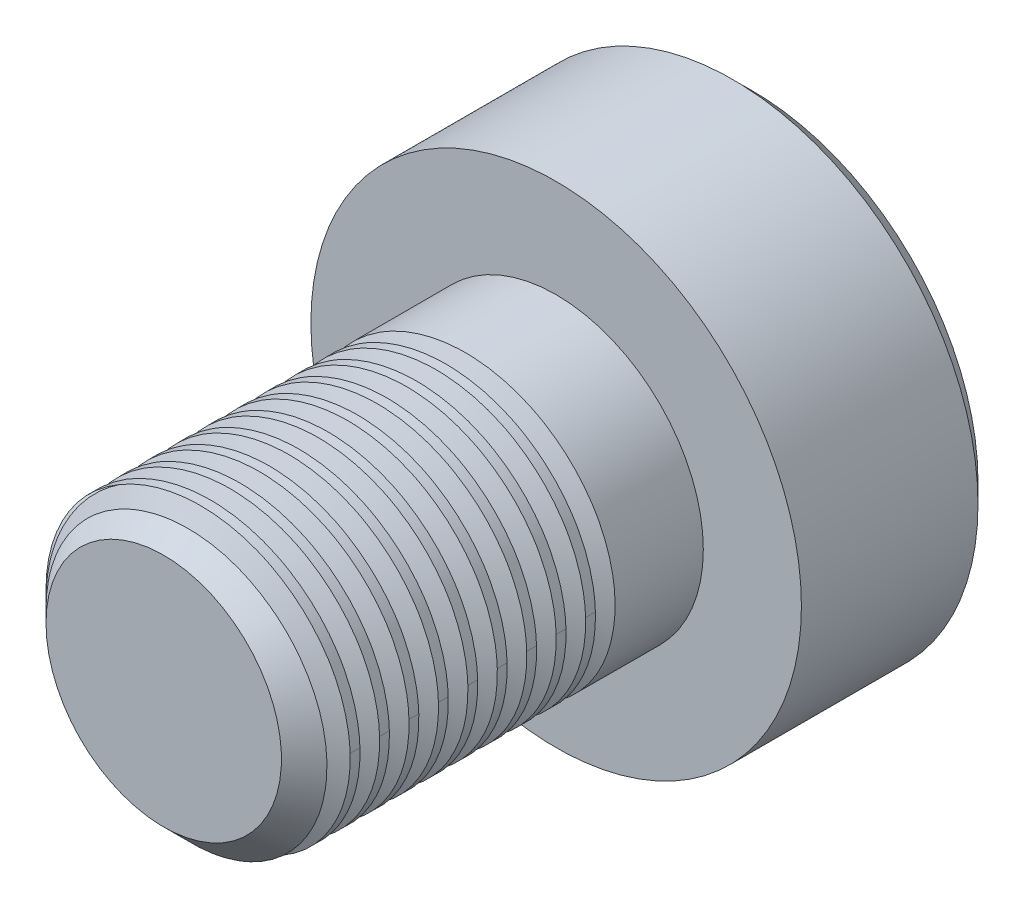
SolidWorks part; units mm, degrees
ref_plane "Front Plane" through (0, 0, 0) normal (0, 0, 1) x (1, 0, 0)
ref_plane "Top Plane" through (0, 0, 0) normal (0, 1, 0) x (1, 0, 0)
ref_plane "Right Plane" through (0, 0, 0) normal (1, 0, 0) x (0, 0, -1)
sketch "Sketch1" plane through (0, 0, 0) normal (0, 1, 0) x (1, 0, 0)
  line L0 (0, 0) -> (0, 34.3069) construction
  line L1 (0, 0) -> (-1.5, 0)
  line L2 (-1.5, 0) -> (-1.5, 4)
  line L3 (-1.5, 4) -> (-2.5, 4)
  line L4 (-2.5, 4) -> (-2.5, 6)
  line L5 (-2.5, 6) -> (0, 6)
  line L6 (0, 0) -> (0, 6)
revolve "Revolve1" add sketch "Sketch1" angle 360 about L0
sketch "Sketch2" plane through (0, 0, -6) normal (0, 0, -1) x (-1, 0, 0)
  line L1 (-2, 0) -> (-1, -1.7321)
  line L2 (-1, -1.7321) -> (1, -1.7321)
  line L3 (1, -1.7321) -> (2, 0)
  line L4 (2, 0) -> (1, 1.7321)
  line L5 (1, 1.7321) -> (-1, 1.7321)
  line L6 (-1, 1.7321) -> (-2, 0)
  circle A0 centre (0, 0) radius 1.7321 construction
extrude "Cut-Extrude1" cut sketch "Sketch2" against normal blind 1.5
fillet "Fillet1" radius 0.2 6 edges at (-1.5, 0.866, -6) (-1.5, -0.866, -6) (0, -1.7321, -6) (1.5, -0.866, -6) (1.5, 0.866, -6) (0, 1.7321, -6)
chamfer "Chamfer1" distance 0.1 angle 45 6 edges at (1.5, -0.866, -4.5) (0, -1.7321, -4.5) (-1.5, -0.866, -4.5) (-1.5, 0.866, -4.5) (0, 1.7321, -4.5) (1.5, 0.866, -4.5)
chamfer "Chamfer2" distance 0.2 angle 45 1 edges at (2.5, 0, -6)
chamfer "Chamfer3" distance 0.3 angle 45 1 edges at (1.5, 0, 0)
sketch "Sketch3" plane through (0, 0, 0) normal (0, 0, 1) x (1, 0, 0)
  circle A0 centre (0, 0) radius 1.3
curve "Helix/Spiral1" pitch 0.3 height 3.075 radius 1.3 centre (0, 0, 0) axis (0, 0, -1) start towards (1, 0, 0)
sketch "Sketch4" plane through (0, 0, 0) normal (0, 1, 0) x (1, 0, 0)
  line L0 (1.5, 0) -> (1.5, 0.1)
  line L1 (1.5, 0) -> (1.5, -0.1)
  line L2 (1.3, -0.01) -> (1.5, -0.1)
  line L3 (1.3, 0.01) -> (1.5, 0.1)
  line L4 (1.3, 0) -> (1.3, -0.01)
  line L5 (1.3, 0) -> (1.3, 0.01)
  spline S1 degree 3 poles (1.3, 0) (1.3, 0.0062) (1.2323, 0.0188) (0.9432, 0.0375) (0.5104, 0.0563) (0, 0.075) (-0.5104, 0.0938) (-0.9432, 0.1125) (-1.2323, 0.1313) (-1.3338, 0.15) (-1.2323, 0.1688) (-0.9432, 0.1875) (-0.5104, 0.2063) (0, 0.225) (0.5104, 0.2438) (0.9432, 0.2625) (1.2323, 0.2813) (1.3338, 0.3) (1.2323, 0.3188) (0.9432, 0.3375) (0.5104, 0.3563) (0, 0.375) (-0.5104, 0.3938) (-0.9432, 0.4125) (-1.2323, 0.4312) (-1.3338, 0.45) (-1.2323, 0.4687) (-0.9432, 0.4875) (-0.5104, 0.5063) (0, 0.525) (0.5104, 0.5437) (0.9432, 0.5625) (1.2323, 0.5812) (1.3338, 0.6) (1.2323, 0.6187) (0.9432, 0.6375) (0.5104, 0.6562) (0, 0.675) (-0.5104, 0.6937) (-0.9432, 0.7125) (-1.2323, 0.7312) (-1.3338, 0.75) (-1.2323, 0.7687) (-0.9432, 0.7875) (-0.5104, 0.8062) (0, 0.825) (0.5104, 0.8437) (0.9432, 0.8625) (1.2323, 0.8812) (1.3338, 0.9) (1.2323, 0.9188) (0.9432, 0.9375) (0.5104, 0.9563) (0, 0.975) (-0.5104, 0.9937) (-0.9432, 1.0125) (-1.2323, 1.0313) (-1.3338, 1.05) (-1.2323, 1.0687) (-0.9432, 1.0875) (-0.5104, 1.1062) (0, 1.125) (0.5104, 1.1438) (0.9432, 1.1625) (1.2323, 1.1813) (1.3338, 1.2) (1.2323, 1.2188) (0.9432, 1.2375) (0.5104, 1.2563) (0, 1.275) (-0.5104, 1.2938) (-0.9432, 1.3125) (-1.2323, 1.3313) (-1.3338, 1.35) (-1.2323, 1.3688) (-0.9432, 1.3875) (-0.5104, 1.4063) (0, 1.425) (0.5104, 1.4438) (0.9432, 1.4625) (1.2323, 1.4813) (1.3338, 1.5) (1.2323, 1.5188) (0.9432, 1.5375) (0.5104, 1.5563) (0, 1.575) (-0.5104, 1.5938) (-0.9432, 1.6125) (-1.2323, 1.6313) (-1.3338, 1.65) (-1.2323, 1.6688) (-0.9432, 1.6875) (-0.5104, 1.7063) (0, 1.725) (0.5104, 1.7438) (0.9432, 1.7625) (1.2323, 1.7813) (1.3338, 1.8) (1.2323, 1.8188) (0.9432, 1.8375) (0.5104, 1.8563) (0, 1.875) (-0.5104, 1.8938) (-0.9432, 1.9125) (-1.2323, 1.9313) (-1.3338, 1.95) (-1.2323, 1.9688) (-0.9432, 1.9875) (-0.5104, 2.0063) (0, 2.025) (0.5104, 2.0438) (0.9432, 2.0625) (1.2323, 2.0813) (1.3338, 2.1) (1.2323, 2.1188) (0.9432, 2.1375) (0.5104, 2.1563) (0, 2.175) (-0.5104, 2.1938) (-0.9432, 2.2125) (-1.2323, 2.2313) (-1.3338, 2.25) (-1.2323, 2.2688) (-0.9432, 2.2875) (-0.5104, 2.3063) (0, 2.325) (0.5104, 2.3438) (0.9432, 2.3625) (1.2323, 2.3813) (1.3338, 2.4) (1.2323, 2.4188) (0.9432, 2.4375) (0.5104, 2.4563) (0, 2.475) (-0.5104, 2.4938) (-0.9432, 2.5125) (-1.2323, 2.5313) (-1.3338, 2.55) (-1.2323, 2.5688) (-0.9432, 2.5875) (-0.5104, 2.6063) (0, 2.625) (0.5104, 2.6438) (0.9432, 2.6625) (1.2323, 2.6813) (1.3338, 2.7) (1.2323, 2.7188) (0.9432, 2.7375) (0.5104, 2.7562) (0, 2.775) (-0.5104, 2.7937) (-0.9432, 2.8125) (-1.2323, 2.8312) (-1.3338, 2.85) (-1.2323, 2.8687) (-0.9432, 2.8875) (-0.5104, 2.9062) (0, 2.925) (0.5104, 2.9437) (0.9432, 2.9625) (1.2323, 2.9812) (1.3338, 3) (1.2323, 3.0187) (0.943, 3.0375) (0.5109, 3.0562) (0.1691, 3.0688) (0, 3.075) knots 0 0 0 0 0.006098 0.012195 0.018293 0.02439 0.030488 0.036585 0.042683 0.04878 0.054878 0.060976 0.067073 0.073171 0.079268 0.085366 0.091463 0.097561 0.103659 0.109756 0.115854 0.121951 0.128049 0.134146 0.140244 0.146341 0.152439 0.158537 0.164634 0.170732 0.176829 0.182927 0.189024 0.195122 0.20122 0.207317 0.213415 0.219512 0.22561 0.231707 0.237805 0.243902 0.25 0.256098 0.262195 0.268293 0.27439 0.280488 0.286585 0.292683 0.29878 0.304878 0.310976 0.317073 0.323171 0.329268 0.335366 0.341463 0.347561 0.353659 0.359756 0.365854 0.371951 0.378049 0.384146 0.390244 0.396341 0.402439 0.408537 0.414634 0.420732 0.426829 0.432927 0.439024 0.445122 0.45122 0.457317 0.463415 0.469512 0.47561 0.481707 0.487805 0.493902 0.5 0.506098 0.512195 0.518293 0.52439 0.530488 0.536585 0.542683 0.54878 0.554878 0.560976 0.567073 0.573171 0.579268 0.585366 0.591463 0.597561 0.603659 0.609756 0.615854 0.621951 0.628049 0.634146 0.640244 0.646341 0.652439 0.658537 0.664634 0.670732 0.676829 0.682927 0.689024 0.695122 0.70122 0.707317 0.713415 0.719512 0.72561 0.731707 0.737805 0.743902 0.75 0.756098 0.762195 0.768293 0.77439 0.780488 0.786585 0.792683 0.79878 0.804878 0.810976 0.817073 0.823171 0.829268 0.835366 0.841463 0.847561 0.853659 0.859756 0.865854 0.871951 0.878049 0.884146 0.890244 0.896341 0.902439 0.908537 0.914634 0.920732 0.926829 0.932927 0.939024 0.945122 0.95122 0.957317 0.963415 0.969512 0.97561 0.981707 0.987805 0.993902 1 1 1 1 construction
sweep "Cut-Sweep3" cut profiles "Sketch4" path "Helix/Spiral1" align with end faces yes
